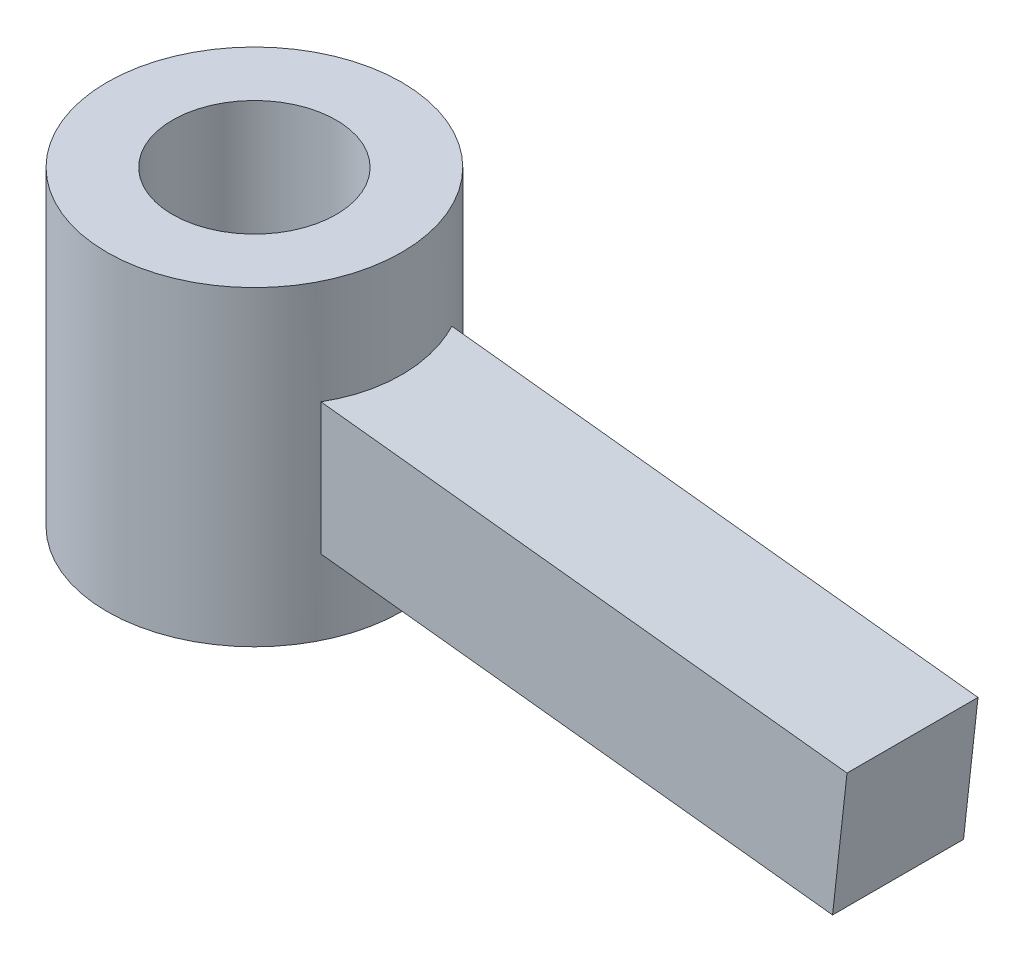
SolidWorks part; units mm, degrees
material "1023 Carbon Steel Sheet (SS)"
ref_plane "Front Plane" through (0, 0, 0) normal (0, 0, 1) x (1, 0, 0)
ref_plane "Top Plane" through (0, 0, 0) normal (0, 1, 0) x (1, 0, 0)
ref_plane "Right Plane" through (0, 0, 0) normal (1, 0, 0) x (0, 0, -1)
sketch "Sketch1" plane through (0, 0, 0) normal (0, 0, 1) x (1, 0, 0)
  line L0 (0, 5.715) -> (0, -5.715)
  arc A0 (0, -5.715) -> (0, 5.715) centre (0, 0) ccw
  dimension "D1" = 11.43
revolve "Revolve1" add sketch "Sketch1" angle 360 about L0
sketch "Sketch2" plane through (0, 0, 0) normal (0, 1, 0) x (1, 0, 0)
  circle A0 centre (0, 0) radius 3.175
  dimension "D1" = 6.35
extrude "Cut-Extrude1" cut sketch "Sketch2" against normal through all both and the other way through all
sketch "Sketch3" plane through (0, 0, 0) normal (0, 1, 0) x (1, 0, 0)
  circle A0 centre (0, 0) radius 3.175 construction
  circle A1 centre (0, 0) radius 3.175
  circle A2 centre (0, 0) radius 5.715
  dimension "D1" = 11.43
extrude "Boss-Extrude1" add sketch "Sketch3" along normal blind 6.0325 and the other way blind 6.0325
ref_axis "Axis1" through (0, 0, -6.2865) along (0, 0, 1)
ref_plane "Plane1" through (0, 0, 0) normal (-0.9939, 0.1104, 0) x (0, 0, 1)
sketch "Sketch4" plane through (0, 0, 0) normal (-0.9939, 0.1104, 0) x (0, 0, -1)
  line L1 (2.54, 2.54) -> (-2.54, 2.54)
  line L2 (2.54, 2.54) -> (2.54, -2.54)
  line L3 (2.54, -2.54) -> (-2.54, -2.54)
  line L4 (-2.54, 2.54) -> (-2.54, -2.54)
  line L5 (2.54, 2.54) -> (-2.54, -2.54) construction
  line L6 (2.54, -2.54) -> (-2.54, 2.54) construction
  point P0 (0, 0)
  dimension "D1" = 5.08
extrude "Boss-Extrude2" add sketch "Sketch4" against normal blind 25.4
